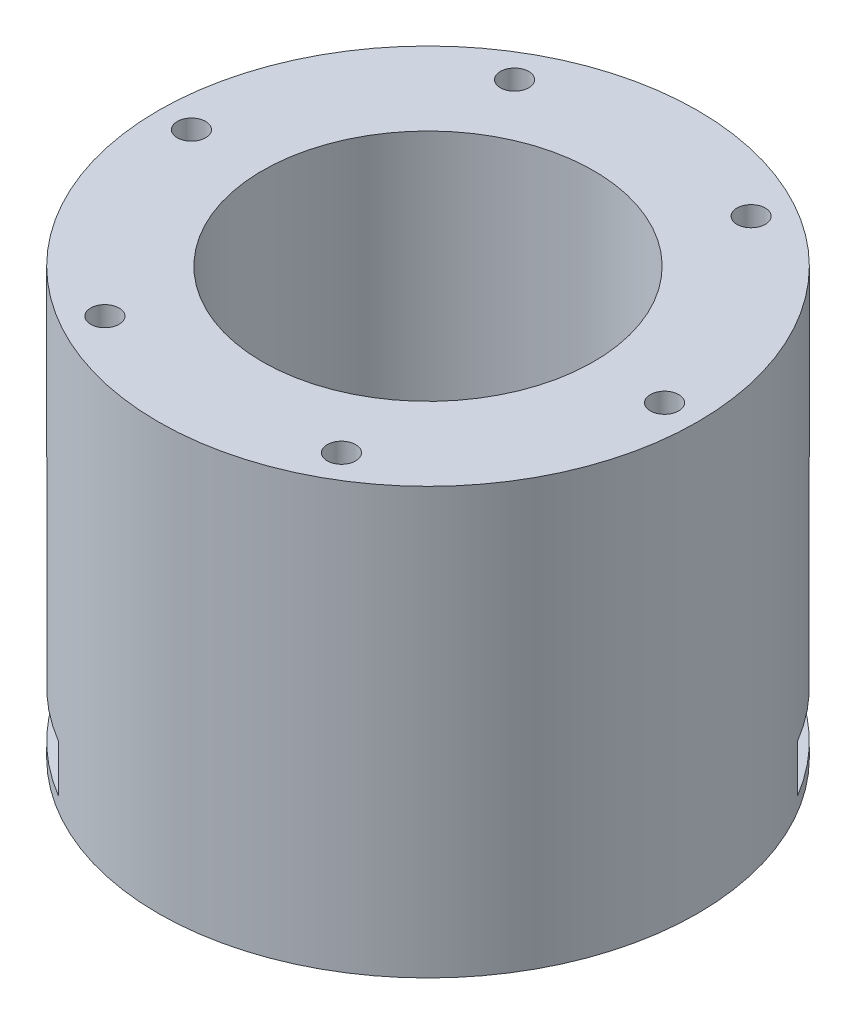
SolidWorks part; units mm, degrees
ref_plane "前视基准面" through (0, 0, 0) normal (0, 0, 1) x (1, 0, 0)
ref_plane "上视基准面" through (0, 0, 0) normal (0, 1, 0) x (1, 0, 0)
ref_plane "右视基准面" through (0, 0, 0) normal (1, 0, 0) x (0, 0, -1)
sketch "草图1" plane through (0, 0, 0) normal (0, 1, 0) x (1, 0, 0)
  circle A0 centre (0, 0) radius 28.5
  circle A1 centre (0, 0) radius 21.25 construction
  dimension "D1" = 57
  dimension "D2" = 42.5
extrude "凸台-拉伸1" add sketch "草图1" along normal blind 45 contours A0
sketch "草图2" plane through (0, 45, 0) normal (0, 1, 0) x (1, 0, 0)
  circle A0 centre (0, 0) radius 17.5
  dimension "D1" = 35
extrude "切除-拉伸1" cut sketch "草图2" against normal blind 30
sketch "草图3" plane through (0, 0, 0) normal (0, -1, 0) x (1, 0, 0)
  circle A0 centre (0, 0) radius 19 construction
  circle A1 centre (-19, 0) radius 1.5
  circle A2 centre (0, 19) radius 1.5
  circle A3 centre (19, 0) radius 1.5
  circle A4 centre (0, -19) radius 1.5
  point P14 (0, 0)
  dimension "D1" = 38
  dimension "D2" = 3
  dimension "D3" = 4
extrude "切除-拉伸2" cut sketch "草图3" against normal blind 6
ref_axis "基准轴1" through (0, 15, 0) along (0, 1, 0)
ref_plane "基准面2" through (0, 0, 0) normal (0.7071, 0, 0.7071) x (0, 1, 0)
ref_plane "基准面3" through (0, 0, 0) normal (0.7071, 0, -0.7071) x (0, 1, 0)
sketch "草图7" plane through (0, 0, 0) normal (0.7071, 0, -0.7071) x (0, 1, 0)
  line L0 (31.7266, 0) -> (-31.7266, 0) construction
  line L1 (6.5, -7) -> (1.5, -7)
  line L2 (6.5, -7) -> (6.5, 7)
  line L3 (6.5, 7) -> (1.5, 7)
  line L4 (1.5, -7) -> (1.5, 7)
  line L6 (0, 28.5) -> (0, -28.5) construction
  dimension "D1" = 7
  dimension "D2" = 14
  dimension "D3" = 5
  dimension "D4" = 1.5
extrude "切除-拉伸3" cut sketch "草图7" against normal mid plane 90 contours L1 L4 L3 L2
sketch "草图8" plane through (0, 0, 0) normal (0.7071, 0, 0.7071) x (0, 1, 0)
  line L0 (-32.5796, 0) -> (32.5796, 0) construction
  line L1 (8.5, 4.5) -> (1.5, 4.5)
  line L2 (8.5, 4.5) -> (8.5, -4.5)
  line L3 (8.5, -4.5) -> (1.5, -4.5)
  line L4 (1.5, 4.5) -> (1.5, -4.5)
  line L5 (0, 28.5) -> (0, -28.5) construction
  dimension "D1" = 7
  dimension "D2" = 9
  dimension "D3" = 4.5
  dimension "D4" = 1.5
extrude "切除-拉伸4" cut sketch "草图8" against normal blind 90 contours L2 L3 L4 L1
sketch "草图9" plane through (0, 45, 0) normal (0, 1, 0) x (1, 0, 0)
  circle A0 centre (0, 0) radius 25 construction
  circle A1 centre (-25, 0) radius 1.5
  circle A2 centre (-12.5, 21.6506) radius 1.5
  circle A3 centre (12.5, 21.6506) radius 1.5
  circle A4 centre (25, 0) radius 1.5
  circle A5 centre (12.5, -21.6506) radius 1.5
  circle A6 centre (-12.5, -21.6506) radius 1.5
  point P11 (0, 0)
  dimension "D1" = 50
  dimension "D2" = 3
  dimension "D3" = 6
extrude "切除-拉伸5" cut sketch "草图9" against normal blind 10
